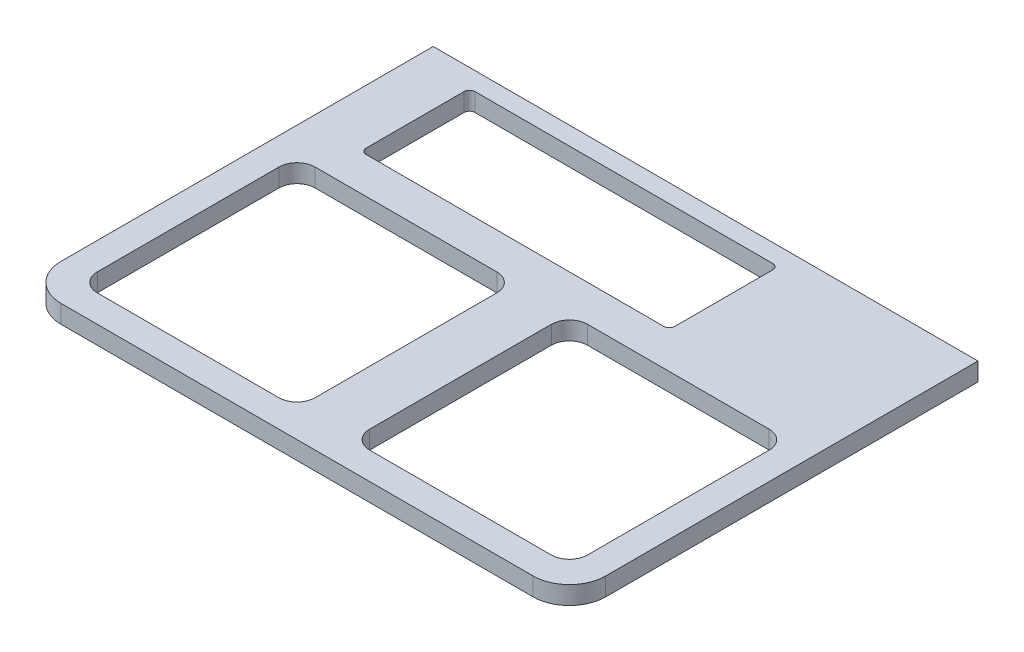
SolidWorks part; units mm, degrees
ref_plane "Ebene vorne" through (0, 0, 0) normal (0, 0, 1) x (1, 0, 0)
ref_plane "Ebene oben" through (0, 0, 0) normal (0, 1, 0) x (1, 0, 0)
ref_plane "Ebene rechts" through (0, 0, 0) normal (1, 0, 0) x (0, 0, -1)
sketch "Skizze1" plane through (0, 10, 0) normal (0, 1, 0) x (1, 0, 0)
  line L0 (-130, -75) -> (130, -75) construction
  line L1 (0, -75) -> (130, -75)
  line L2 (0, -75) -> (0, 75)
  line L3 (0, 75) -> (150, 75) construction
  line L4 (150, -55) -> (150, 75)
  line L5 (150, -55) -> (150, 150) construction
  line L6 (15, -60) -> (15, -75) construction
  line L7 (15, 60) -> (135, 60)
  line L8 (15, 60) -> (15, -60)
  line L9 (15, -60) -> (135, -60)
  line L10 (135, 60) -> (135, -60)
  line L11 (15, -75) -> (15, -60) construction
  line L12 (0, -60) -> (15, -60) construction
  line L13 (135, 60) -> (135, 75) construction
  line L14 (135, 60) -> (150, 60) construction
  line L15 (150, 75) -> (150, 150)
  line L16 (150, 150) -> (0, 150)
  line L17 (0, 150) -> (0, 75)
  arc A0 (130, -75) -> (150, -55) centre (130, -55) ccw
  arc A1 (130, -75) -> (150, -55) centre (130, -55) ccw construction
  dimension "D1" = 120
extrude "Linear austragen1" add sketch "Skizze1" along normal blind 10
fillet "Verrundung2" radius 10 4 edges at (15, 15, 60) (135, 15, 60) (135, 15, -60) (15, 15, -60)
mirror "Spiegeln1" about plane through (0, 20, -150) normal (1, 0, 0) of "Verrundung2", "Linear austragen1"
sketch "Skizze3" plane through (0, 10, 0) normal (0, -1, 0) x (1, 0, 0)
  line L0 (-150, 55) -> (-150, -150) construction
  line L1 (-120, -80) -> (50, -80)
  line L2 (-120, -80) -> (-120, -140)
  line L3 (-120, -140) -> (50, -140)
  line L4 (50, -80) -> (50, -140)
  line L5 (150, -150) -> (-150, -150) construction
  line L6 (0, -60.4164) -> (0, -150) construction
  dimension "D1" = 30
  dimension "D2" = 10
  dimension "D3" = 50
  dimension "D4" = 60
extrude "Schnitt-Linear austragen1" cut sketch "Skizze3" against normal blind 10
fillet "Verrundung3" radius 3 4 edges at (-120, 15, -140) (50, 15, -140) (50, 15, -80) (-120, 15, -80)
